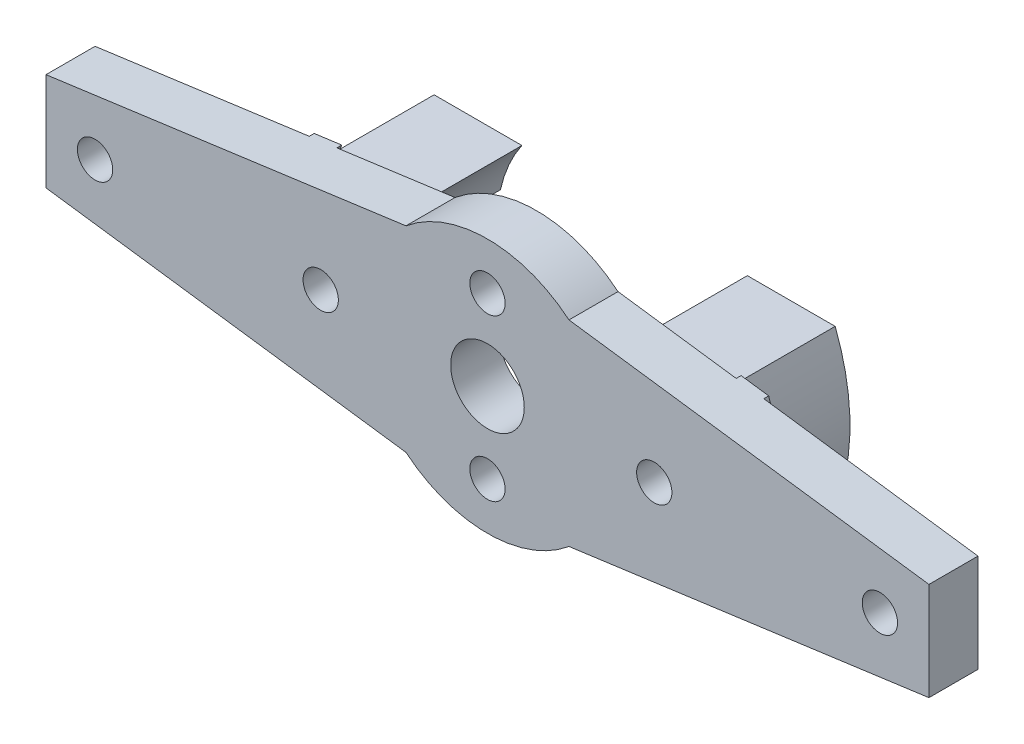
SolidWorks part; units mm, degrees
ref_plane "正面" through (0, 0, 0) normal (0, 0, 1) x (1, 0, 0)
ref_plane "平面" through (0, 0, 0) normal (0, 1, 0) x (1, 0, 0)
ref_plane "右側面" through (0, 0, 0) normal (1, 0, 0) x (0, 0, -1)
sketch "ｽｹｯﾁ1" plane through (0, 0, 0) normal (0, 0, 1) x (1, 0, 0)
  line L1 (-45, 10) -> (45, 10)
  line L2 (-45, 10) -> (-45, -10)
  line L3 (-45, -10) -> (45, -10)
  line L4 (45, 10) -> (45, -10)
  line L5 (-45, 10) -> (45, -10) construction
  line L6 (-45, -10) -> (45, 10) construction
  point P0 (0, 0)
  dimension "D1" = 90
  dimension "D2" = 20
extrude "ﾎﾞｽ - 押し出し1" add sketch "ｽｹｯﾁ1" along normal blind 5
sketch "ｽｹｯﾁ2" plane through (0, 0, 5) normal (0, 0, 1) x (1, 0, 0)
  line L0 (45, 10) -> (-45, 10) construction
  line L1 (-35, 10) -> (-22, 10)
  line L2 (-35, 10) -> (-35, -10)
  line L3 (-35, -10) -> (-22, -10)
  line L4 (-22, 10) -> (-22, -10)
  line L5 (-45, -10) -> (45, -10) construction
  line L6 (-45, 10) -> (-45, -10) construction
  line L7 (22, 10) -> (35, 10)
  line L8 (22, 10) -> (22, -10)
  line L9 (22, -10) -> (35, -10)
  line L10 (35, 10) -> (35, -10)
  line L11 (45, -10) -> (45, 10) construction
  dimension "D1" = 10
  dimension "D2" = 10
  dimension "D3" = 22
  dimension "D4" = 22
sketch "ｽｹｯﾁ4" plane through (0, 0, 5) normal (0, 0, 1) x (1, 0, 0)
  circle A0 centre (0, 0) radius 3.75
  circle A3 centre (0, 8.2) radius 1.8
  circle A4 centre (0, -8.1958) radius 1.8
  circle A5 centre (0, 0) radius 13
  dimension "D1" = 7.5
  dimension "D4" = 3.6
  dimension "D5" = 26
  dimension "D2" = 8.2
  dimension "D3" = 8.1958
extrude "ﾎﾞｽ - 押し出し3" add sketch "ｽｹｯﾁ4" against normal up to surface (5 mm away) up to face at (0, 0, 0)
sketch "ｽｹｯﾁ3" plane through (0, 0, 5) normal (0, 0, 1) x (1, 0, 0)
  line L0 (-45, 0) -> (45, 0) construction
  line L1 (-45, 10) -> (-45, -10) construction
  line L2 (45, -10) -> (45, 10) construction
  circle A0 centre (-40, 0) radius 1.8
  circle A1 centre (-17, 0) radius 1.8
  circle A2 centre (17, 0) radius 1.8
  circle A3 centre (40, 0) radius 1.8
  point P14 (0, 0)
  point P17 (10.6241, 12.1765)
  dimension "D1" = 3.6
  dimension "D2" = 5
  dimension "D3" = 17
  dimension "D4" = 17
  dimension "D5" = 5
extrude "ｶｯﾄ - 押し出し1" cut sketch "ｽｹｯﾁ3" against normal through all
extrude "ｶｯﾄ - 押し出し3" cut sketch "ｽｹｯﾁ4<3>" against normal through all contours A0 | A3 | A4 region at (0, 0, 5)
sketch "ｽｹｯﾁ4<3>" plane through (0, 0, 5) normal (0, 0, 1) x (1, 0, 0) same geometry as "ｽｹｯﾁ4"
sketch "ｽｹｯﾁ6" plane through (0, 0, 0) normal (0, 0, -1) x (-1, 0, 0)
  line L0 (45, -10) -> (8.3066, -10) construction
  line L1 (8.3066, 10) -> (45, 10) construction
  line L2 (-45, 10) -> (-8.3066, 10) construction
  line L3 (-8.3066, -10) -> (-45, -10) construction
  line L4 (-19.5398, 10) -> (-9.798, 10)
  line L5 (-19.5398, -10) -> (-9.798, -10)
  line L6 (9.798, 10) -> (19.5398, 10)
  line L7 (9.798, -10) -> (19.5398, -10)
  arc A0 (9.798, 10) -> (9.798, -10) centre (0, 0) cw
  arc A2 (-9.798, 10) -> (-9.798, -10) centre (0, 0) ccw
  arc A3 (19.5398, 10) -> (19.5398, -10) centre (0, 0) cw
  arc A4 (-19.5398, 10) -> (-19.5398, -10) centre (0, 0) ccw
  dimension "D1" = 14
  dimension "D2" = 14
  dimension "D3" = 21.95
  dimension "D4" = 21.95
extrude "ﾎﾞｽ - 押し出し4" add sketch "ｽｹｯﾁ6" along normal blind 10
sketch "ｽｹｯﾁ8" plane through (0, 0, -10) normal (0, 0, -1) x (-1, 0, 0)
  line L1 (-22.364, 17.9252) -> (24.0397, 17.9252)
  line L2 (-22.364, 17.9252) -> (-22.364, 8)
  line L3 (-22.364, 8) -> (24.0397, 8)
  line L4 (24.0397, 17.9252) -> (24.0397, 8)
  line L5 (24.0397, -8) -> (-22.364, -8)
  line L6 (24.0397, -8) -> (24.0397, -15.9918)
  line L7 (24.0397, -15.9918) -> (-22.364, -15.9918)
  line L8 (-22.364, -8) -> (-22.364, -15.9918)
  dimension "D1" = 8
  dimension "D2" = 8
extrude "ｶｯﾄ - 押し出し4" cut sketch "ｽｹｯﾁ8" against normal up to surface (10 mm away) up to face at (32.8724, 0, 0)
sketch "ｽｹｯﾁ9" plane through (0, 0, 5) normal (0, 0, 1) x (1, 0, 0)
  line L1 (8.3066, -10) -> (45, -5)
  line L2 (45, -10) -> (45, 10) construction
  line L4 (45, 5) -> (8.3066, 10)
  line L5 (8.3066, -10) -> (45, -10) construction
  line L6 (8.3066, 10) -> (45, 10)
  line L7 (45, 10) -> (8.3066, 10) construction
  line L8 (45, 10) -> (45, 5)
  line L9 (45, -5) -> (45, -10)
  line L10 (45, -10) -> (8.3066, -10)
  line L11 (-8.3066, 10) -> (-45, 10)
  line L12 (-8.3066, 10) -> (-45, 10) construction
  line L13 (-45, 10) -> (-45, 5)
  line L14 (-45, 10) -> (-45, -10) construction
  line L15 (-45, 5) -> (-8.3066, 10)
  line L16 (-8.3066, -10) -> (-45, -10)
  line L17 (-45, -10) -> (-45, -5)
  line L18 (-45, -5) -> (-8.3066, -10)
  dimension "D1" = 5
  dimension "D2" = 5
  dimension "D3" = 5
  dimension "D4" = 5
extrude "ｶｯﾄ - 押し出し5" cut sketch "ｽｹｯﾁ9" against normal through all and the other way blind 10
sketch "ｽｹｯﾁ12" plane through (0, 0, -10) normal (0, 0, -1) x (-1, 0, 0)
  line L1 (-17.5, 3) -> (17.5, 3)
  line L3 (-17.5, -3) -> (17.5, -3)
  line L5 (-17.5, 3) -> (17.5, -3) construction
  line L6 (-17.5, -3) -> (17.5, 3) construction
  arc A0 (17.5, 3) -> (17.5, -3) centre (17.5, 0) cw
  arc A1 (-17.5, -3) -> (-17.5, 3) centre (-17.5, 0) cw
  point P0 (0, 0)
  dimension "D1" = 6
  dimension "D2" = 35
extrude "ｶｯﾄ - 押し出し6" cut sketch "ｽｹｯﾁ12" against normal up to surface (10 mm away) up to face at (1.8, 8.2, 0)
sketch "ｽｹｯﾁ13" plane through (0, 0, 0) normal (0, 0, -1) x (-1, 0, 0)
  line L0 (-45, 5) -> (-8.3066, 10) construction
  line L1 (-8.3066, -10) -> (-45, -5) construction
  line L2 (45, -5) -> (8.3066, -10) construction
  line L3 (8.3066, 10) -> (45, 5) construction
  line L4 (-23.1656, 7.9752) -> (-20.3502, 8.3589)
  line L6 (20.3502, 8.3589) -> (23.1656, 7.9752)
  line L7 (23.1656, -7.9752) -> (20.3502, -8.3589)
  line L8 (-20.3502, -8.3589) -> (-22, -8.1341)
  arc A0 (-23.1656, 7.9752) -> (-23.1656, -7.9752) centre (0, 0) ccw
  arc A1 (23.1656, -7.9752) -> (23.1656, 7.9752) centre (0, 0) ccw
  arc A2 (-20.3502, 8.3589) -> (-20.3502, -8.3589) centre (0, 0) ccw
  arc A3 (20.3502, -8.3589) -> (20.3502, 8.3589) centre (0, 0) ccw
  arc M5 (20.4402, 8) -> (20.4402, -8) centre (0, 0) cw
  arc M18 (-20.4402, -8) -> (-20.4402, 8) centre (0, 0) cw
  line M22 (-45, -5) -> (-8.3066, -10)
  line M24 (8.3066, -10) -> (45, -5)
  line M26 (45, 5) -> (8.3066, 10)
  line M28 (-8.3066, 10) -> (-45, 5)
  dimension "D1" = 24.5
  dimension "D2" = 22
  dimension "D3" = 24.5
  dimension "D4" = 22
extrude "ﾎﾞｽ - 押し出し5" add sketch "ｽｹｯﾁ13" along normal blind 0.5 contours A2 A0 M28 M22 M18 | A3 A1 M5 M24 M26 region at (22.7412, 0, 0) region at (-22.7412, 0, 0)
